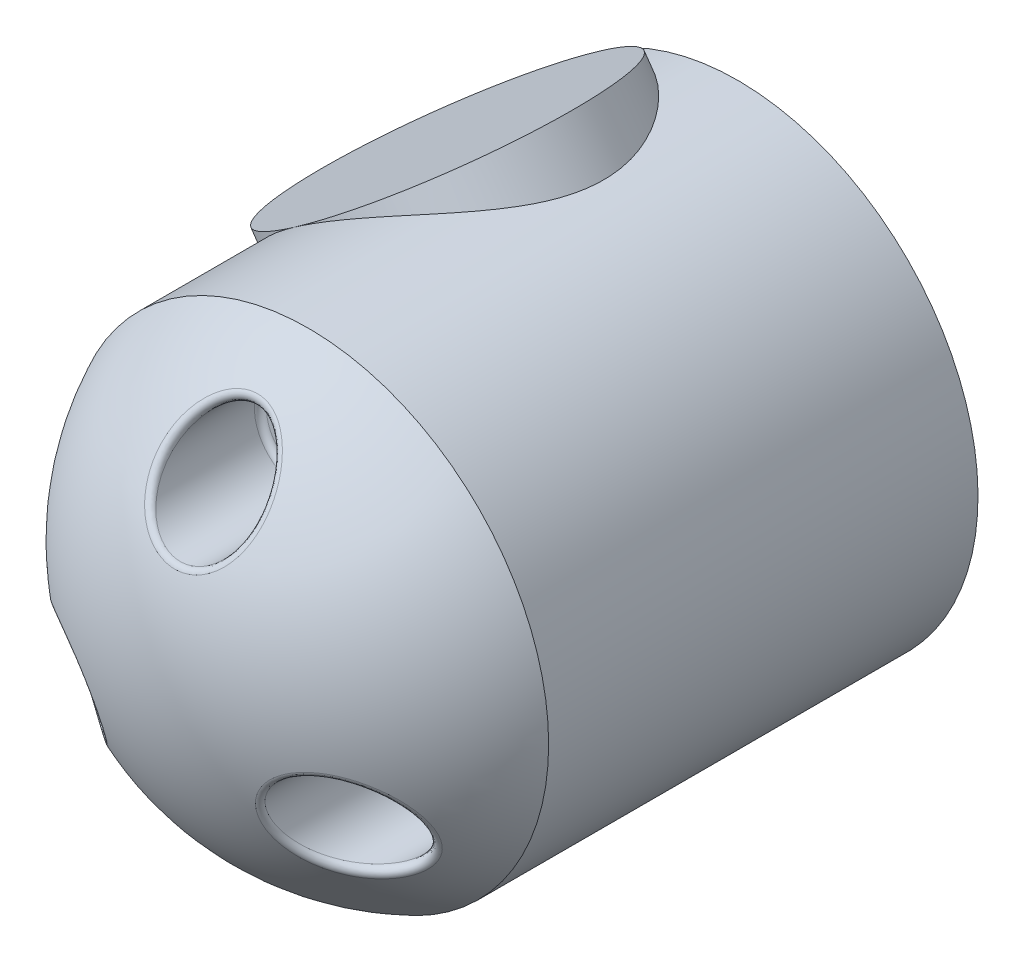
SolidWorks part; units mm, degrees
ref_plane "Front Plane" through (0, 0, 0) normal (0, 0, 1) x (1, 0, 0)
ref_plane "Top Plane" through (0, 0, 0) normal (0, 1, 0) x (1, 0, 0)
ref_plane "Right Plane" through (0, 0, 0) normal (1, 0, 0) x (0, 0, -1)
sketch "Sketch1" plane through (0, 0, 0) normal (0, 0, 1) x (1, 0, 0)
  circle A0 centre (0, 0) radius 10
  dimension "D1" = 20
extrude "Boss-Extrude1" add sketch "Sketch1" along normal blind 2
dome "Dome1" faces to dome 1 distance 6.35 reverse direction no elliptical dome no face at (10, 0, 2) parameters "D1"=6.35
sketch "Sketch2" plane through (0, 0, 0) normal (0, 0, -1) x (-1, 0, 0)
  line L0 (0, 0) -> (0, 6.25) construction
  circle A0 centre (0, 6.25) radius 1.1
  circle A1 centre (5.4127, -3.125) radius 1.1
  circle A2 centre (-5.4127, -3.125) radius 1.1
  circle A3 centre (0, 0) radius 6.25 construction
  point P10 (0, 0)
  dimension "D2" = 2.2
  dimension "D1" = 6.25
  dimension "D3" = 3
extrude "Cut-Extrude1" cut sketch "Sketch2" against normal through all
ref_plane "Plane1" through (0, 0, 2) normal (0, 0, 1) x (1, 0, 0)
sketch "Sketch3" plane through (0, 0, 2) normal (0, 0, 1) x (1, 0, 0)
  circle A0 centre (0, 6.25) radius 2
  circle A1 centre (5.4127, -3.125) radius 2
  circle A2 centre (-5.4127, -3.125) radius 2
  dimension "D1" = 4
extrude "Cut-Extrude2" cut sketch "Sketch3" along normal through all
sketch "Sketch4" plane through (0, 0, 0) normal (0, 0, -1) x (-1, 0, 0)
  circle A0 centre (0, 0) radius 10
  circle A1 centre (0, 0) radius 9.5
  circle A2 centre (0, 0) radius 10 construction
  dimension "D1" = 0.5
extrude "Boss-Extrude2" add sketch "Sketch4" along normal blind 15.875
fillet "Fillet1" radius 0.5 1 edges at (-9.5, 0, 0)
fillet "Fillet2" radius 0.25 6 edges at (-4.3127, -3.125, 2) (-3.4127, -3.125, 2) (6.5127, -3.125, 2) (7.4127, -3.125, 2) (1.1, 6.25, 2) (2, 6.25, 2)
fillet "Fillet3" radius 0.25 3 edges at (-3.7506, -2.0126, 7.4972) (4.214, -1.524, 7.4005) (0.834, 4.4322, 7.3877)
sketch "Sketch5" plane through (0, 0, 0) normal (0, 1, 0) x (1, 0, 0)
  line L0 (4.0438, 22.225) -> (4.0438, 9.525) construction
  line L1 (7.2188, 22.225) -> (7.2188, 9.525)
  line L2 (0.8688, 22.225) -> (0.8688, 9.525)
  line L3 (9.5, 15.875) -> (-9.5, 15.875) construction
  line L4 (10, -2) -> (-10, -2) construction
  line L5 (10, 15.875) -> (-10, 15.875) construction
  arc A0 (7.2188, 22.225) -> (0.8688, 22.225) centre (4.0438, 22.225) ccw
  arc A1 (0.8688, 9.525) -> (7.2188, 9.525) centre (4.0438, 9.525) ccw
  point P2 (4.0438, 15.875)
  point P7 (4.0438, 6.35)
  dimension "D1" = 6.35
  dimension "D2" = 8.35
extrude "Cut-Extrude3" cut sketch "Sketch5" against normal through all
ref_plane "Plane2" through (-5.7358, 8.1915, 0) normal (-0.5736, 0.8192, 0) x (0.8192, 0.5736, 0)
sketch "Sketch6" plane through (-5.7358, 8.1915, 0) normal (-0.5736, 0.8192, 0) x (0.8192, 0.5736, 0)
  line L0 (10, 15.875) -> (-10, 15.875) construction
  line L1 (0, 9.525) -> (0, 15.875) construction
  line L2 (9.5, 15.875) -> (-9.5, 15.875) construction
  circle A0 centre (0, 9.525) radius 6.35
  dimension "D1" = 12.7
extrude "Boss-Extrude3" add sketch "Sketch6" against normal up to surface (2.9341 mm away) up to face at (1.9822, -3.929, -11.9073)
